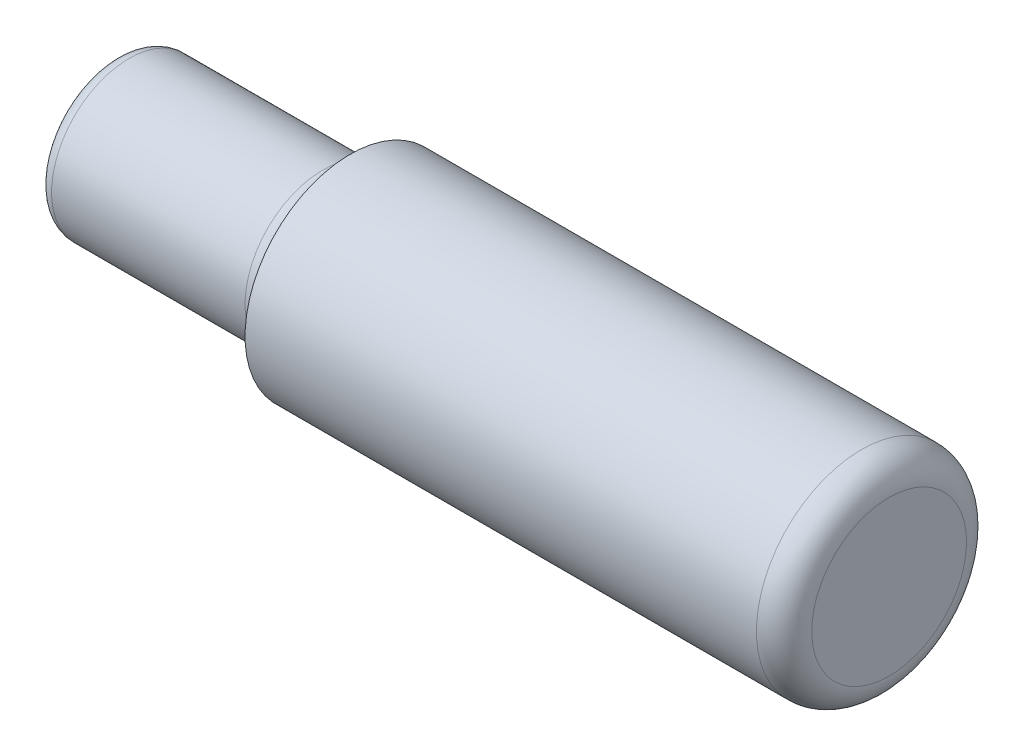
SolidWorks part; units mm, degrees
ref_plane "Alzado" through (0, 0, 0) normal (1, 0, 0) x (0, 1, 0)
ref_plane "Planta" through (0, 0, 0) normal (0, 0, 1) x (0, 1, 0)
ref_plane "Vista lateral" through (0, 0, 0) normal (0, 1, 0) x (-1, 0, 0)
sketch "Croquis1" plane through (0, 0, 0) normal (1, 0, 0) x (0, 1, 0)
  circle A0 centre (0, 0) radius 3.8
  circle A1 centre (0, 0) radius 2.8
  dimension "D1" = 7.6
  dimension "D2" = 5.6
extrude "Saliente-Extruir1" add sketch "Croquis1" along normal blind 19.5 contours A1 | A0 A1 region at (0, -3.6925, 0) region at (0, 0, 0)
extrude "Saliente-Extruir2" add sketch "Croquis1<4>" against normal blind 8.5 contours A1 region at (0, 0, 0)
sketch "Croquis1<4>" plane through (0, 0, 0) normal (1, 0, 0) x (0, 1, 0) same geometry as "Croquis1"
fillet "Redondeo1" radius 1 2 edges at (19.5, 0, -3.8) (0, 0, -2.8)
fillet "Redondeo2" radius 0.5 1 edges at (-8.5, 0, -2.8)
